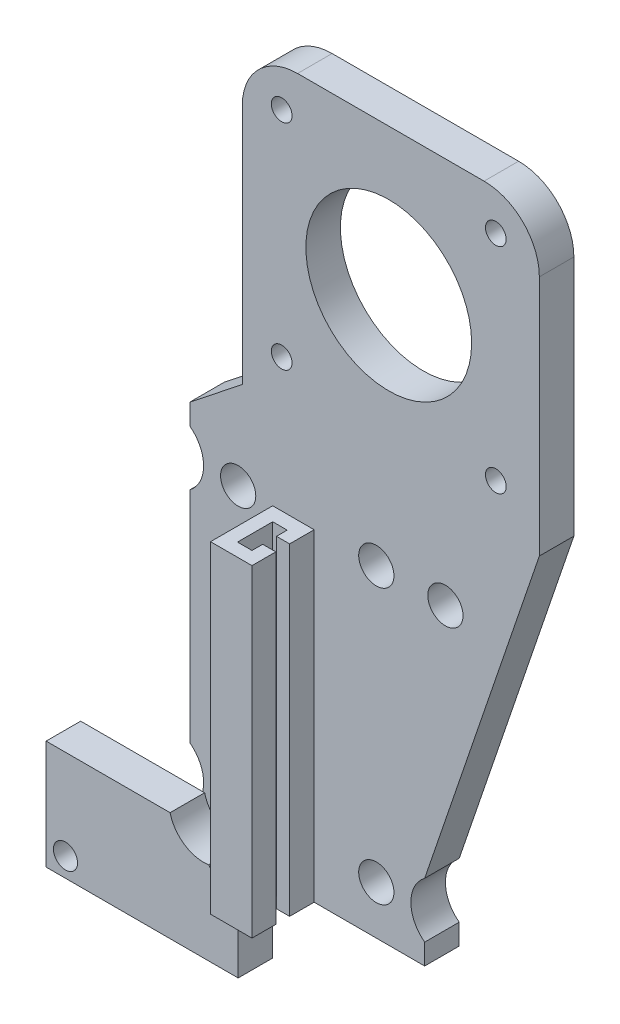
SolidWorks part; units mm, degrees
ref_plane "Front Plane" through (0, 0, 0) normal (0, 0, 1) x (1, 0, 0)
ref_plane "Top Plane" through (0, 0, 0) normal (0, 1, 0) x (1, 0, 0)
ref_plane "Right Plane" through (0, 0, 0) normal (1, 0, 0) x (0, 0, -1)
sketch "Sketch1" plane through (0, 0, 0) normal (0, 0, 1) x (1, 0, 0)
  line L0 (7, 46.7) -> (27, 46.7) construction
  line L1 (0, 0) -> (34, 0)
  line L2 (0, 0) -> (0, 3)
  line L3 (0, 53.7) -> (34, 53.7)
  line L4 (34, 0) -> (34, 3)
  line L5 (27, 46.7) -> (27, 7) construction
  line L6 (27, 7) -> (7, 7) construction
  line L7 (7, 7) -> (7, 46.7) construction
  line L8 (-3, 46.7) -> (37, 46.7) construction
  line L9 (37, 46.7) -> (37, 7) construction
  line L10 (37, 7) -> (-3, 7) construction
  line L11 (-3, 7) -> (-3, 46.7) construction
  line L12 (0, 50.7) -> (0, 53.7)
  line L13 (34, 50.7) -> (34, 53.7)
  line L14 (34, 11) -> (34, 42.7)
  line L15 (0, 11) -> (0, 42.7)
  circle A0 centre (7, 46.7) radius 2.55
  circle A1 centre (27, 46.7) radius 2.55
  circle A2 centre (7, 7) radius 2.55
  circle A3 centre (27, 7) radius 2.55
  arc A4 (0, 42.7) -> (0, 50.7) centre (-3, 46.7) ccw
  arc A5 (34, 50.7) -> (34, 42.7) centre (37, 46.7) ccw
  arc A6 (34, 11) -> (34, 3) centre (37, 7) ccw
  arc A7 (0, 3) -> (0, 11) centre (-3, 7) ccw
  dimension "D3" = 5.1
  dimension "D10" = 10
  dimension "D1" = 20
  dimension "D2" = 39.7
  dimension "D4" = 7
  dimension "D5" = 7
  dimension "D6" = 7
  dimension "D7" = 7
  dimension "D8" = 10
  dimension "D9" = 10
extrude "Boss-Extrude1" add sketch "Sketch1" along normal blind 5
sketch "Sketch2" plane through (0, 0, 5) normal (0, 0, 1) x (1, 0, 0)
  line L0 (7, 46.7) -> (27, 46.7) construction
  line L1 (12, 46.7) -> (18, 46.7)
  line L2 (12, 46.7) -> (12, 0)
  line L3 (12, 0) -> (18, 0)
  line L4 (18, 46.7) -> (18, 0)
  line L5 (7, 7) -> (27, 7) construction
  line L6 (17, 53.7) -> (17, 0) construction
  line L7 (34, 53.7) -> (0, 53.7) construction
  line L8 (0, 0) -> (34, 0) construction
  line L9 (0, 42.7) -> (0, 11) construction
  circle A0 centre (7, 7) radius 2.55 construction
  circle A1 centre (27, 7) radius 2.55 construction
  circle A2 centre (27, 46.7) radius 2.55 construction
  circle A3 centre (7, 46.7) radius 2.55 construction
  circle A4 centre (7, 7) radius 2.55
  circle A5 centre (27, 7) radius 2.55
  circle A6 centre (27, 46.7) radius 2.55
  circle A7 centre (7, 46.7) radius 2.55
  dimension "D1" = 6
  dimension "D2" = 12
extrude "Boss-Extrude2" add sketch "Sketch2" along normal blind 9 contours L4 L1 L2 L3 region at (15, 23.35, 5)
sketch "Sketch3" plane through (0, 0, 5) normal (0, 0, 1) x (1, 0, 0)
  line L0 (12, 46.7) -> (12, 0) construction
  line L1 (12, 5.8) -> (11.8539, 5.8)
  line L2 (12, 5.8) -> (12, -10)
  line L3 (12, -10) -> (-15.8, -10)
  line L4 (-15.8, 5.8) -> (-15.8, -10)
  line L6 (0, 0) -> (12, 0) construction
  line L7 (2.1461, 5.8) -> (-15.8, 5.8)
  circle A0 centre (7, 7) radius 4
  arc A1 (2.1461, 5.8) -> (11.8539, 5.8) centre (7, 7) ccw
  line M8 (12, 0) -> (12, 46.7)
  line M12 (0, 3) -> (0, 0)
  line M13 (0, 0) -> (12, 0)
  arc M23 (0, 11) -> (0, 3) centre (-3, 7) cw
  dimension "D3" = 8
  dimension "D5" = 10
  dimension "D1" = 27.8
  dimension "D2" = 15.8
  dimension "D4" = 10
extrude "Boss-Extrude3" add sketch "Sketch3" along normal blind 5 contours L1 L4 L3 L2 M13 M12 M23 | A0 L1 M23 M12 M13 M8 region at (5.7392, 1.8198, 5) region at (-3.3519, -2.9735, 5)
sketch "Sketch4" plane through (0, 0, 10) normal (0, 0, 1) x (1, 0, 0)
  line L0 (12, 5.8) -> (11.8539, 5.8) construction
  line L1 (-15.8, 5.8) -> (-15.8, -10) construction
  line L2 (12, 0) -> (12, -10) construction
  line L3 (12, -10) -> (-15.8, -10) construction
  circle A0 centre (9.2, 3) radius 1.75
  circle A1 centre (-13, -7.2) radius 1.75
  dimension "4" = 3.5
  dimension "D1" = 2.8
  dimension "D2" = 2.8
  dimension "D3" = 2.8
  dimension "D4" = 2.8
extrude "Cut-Extrude1" cut sketch "Sketch4" against normal through all
sketch "Sketch5" plane through (0, 46.7, 0) normal (0, 1, 0) x (1, 0, 0)
  line L0 (18, -8.55) -> (16.1, -8.55)
  line L9 (18, -14) -> (18, -5) construction
  line L10 (16.1, -8.55) -> (16.1, -7)
  line L11 (16.1, -7) -> (14, -7)
  line L12 (14, -7) -> (14, -12.1)
  line L13 (14, -12.1) -> (16.1, -12.1)
  line L14 (16.1, -12.1) -> (16.1, -10.55)
  line L15 (16.1, -10.55) -> (18, -10.55)
  line L16 (12, -9.55) -> (18, -9.55) construction
  line L18 (12, -5) -> (18, -5) construction
  dimension "D1" = 1.9
  dimension "D2" = 2
  dimension "D3" = 5.1
  dimension "D4" = 2.1
  dimension "D5" = 2
extrude "Cut-Extrude2" cut sketch "Sketch5" against normal through all and the other way through all
sketch "Sketch6" plane through (0, 0, 5) normal (0, 0, 1) x (1, 0, 0)
  line L0 (0, 53.7) -> (0, 50.7) construction
  line L5 (7.6, 102.7) -> (50.6, 102.7)
  line L6 (7.6, 102.7) -> (7.6, 59.7)
  line L7 (7.6, 59.7) -> (50.6, 59.7)
  line L8 (50.6, 102.7) -> (50.6, 59.7)
  line L9 (7.6, 59.7) -> (0, 53.7)
  line L10 (0, 53.7) -> (34, 53.7)
  line L11 (34, 53.7) -> (50.6, 59.7)
  circle A0 centre (27, 46.7) radius 2.55 construction
  line M23 (34, 53.7) -> (0, 53.7)
  dimension "D3" = 13
  dimension "D1" = 43
  dimension "D2" = 43
  dimension "D4" = 7.6
extrude "Boss-Extrude4" add sketch "Sketch6" against normal through all contours L8 L5 L6 L7 | L11 L7 L9 M23 region at (29.1, 81.2, 5) region at (23.2857, 56.8169, 5)
sketch "Sketch8" plane through (0, 0, 5) normal (0, 0, 1) x (1, 0, 0)
  line L0 (13.3, 97) -> (44.3, 97) construction
  line L1 (44.3, 97) -> (44.3, 66) construction
  line L2 (44.3, 66) -> (13.3, 66) construction
  line L3 (13.3, 66) -> (13.3, 97) construction
  line L4 (7.6, 102.7) -> (7.6, 59.7) construction
  line L5 (7.6, 102.7) -> (50.6, 102.7) construction
  line L6 (28.8, 97) -> (28.8, 66) construction
  line L7 (13.3, 81.5) -> (44.3, 81.5) construction
  circle A0 centre (13.3, 97) radius 1.5
  circle A1 centre (44.3, 97) radius 1.5
  circle A2 centre (13.3, 66) radius 1.5
  circle A3 centre (44.3, 66) radius 1.5
  circle A4 centre (28.8, 81.5) radius 12
  point P18 (28.8, 81.5)
  dimension "D5" = 3
  dimension "D6" = 24
  dimension "D1" = 5.7
  dimension "D2" = 5.7
  dimension "D3" = 31
  dimension "D4" = 31
extrude "Cut-Extrude3" cut sketch "Sketch8" against normal through all
sketch "Sketch9" plane through (0, 0, 5) normal (0, 0, 1) x (1, 0, 0)
  line L0 (50.6, 59.7) -> (34, 11)
  circle A0 centre (37, 46.7) radius 5
  line M18 (34, 11) -> (34, 42.7)
  line M20 (34, 50.7) -> (34, 53.7)
  line M21 (34, 53.7) -> (50.6, 59.7)
  dimension "D1" = 10
extrude "Boss-Extrude5" add sketch "Sketch9" against normal up to surface (5 mm away) contours A0 L0 M18 M21 M20 region at (39.9791, 40.2387, 5) up to face at (45.8, 97, 0)
sketch "Sketch10" plane through (0, 0, 5) normal (0, 0, 1) x (1, 0, 0)
  circle A0 centre (37, 46.7) radius 2.55
  circle A1 centre (37, 46.7) radius 5 construction
  circle A2 centre (37, 46.7) radius 5
  dimension "D1" = 5.1
extrude "Boss-Extrude6" add sketch "Sketch10" against normal up to surface (5 mm away) up to face at (42, 46.7, 0)
fillet "Fillet1" radius 8 2 edges at (7.6, 102.7, 2.5) (50.6, 102.7, 2.5)
